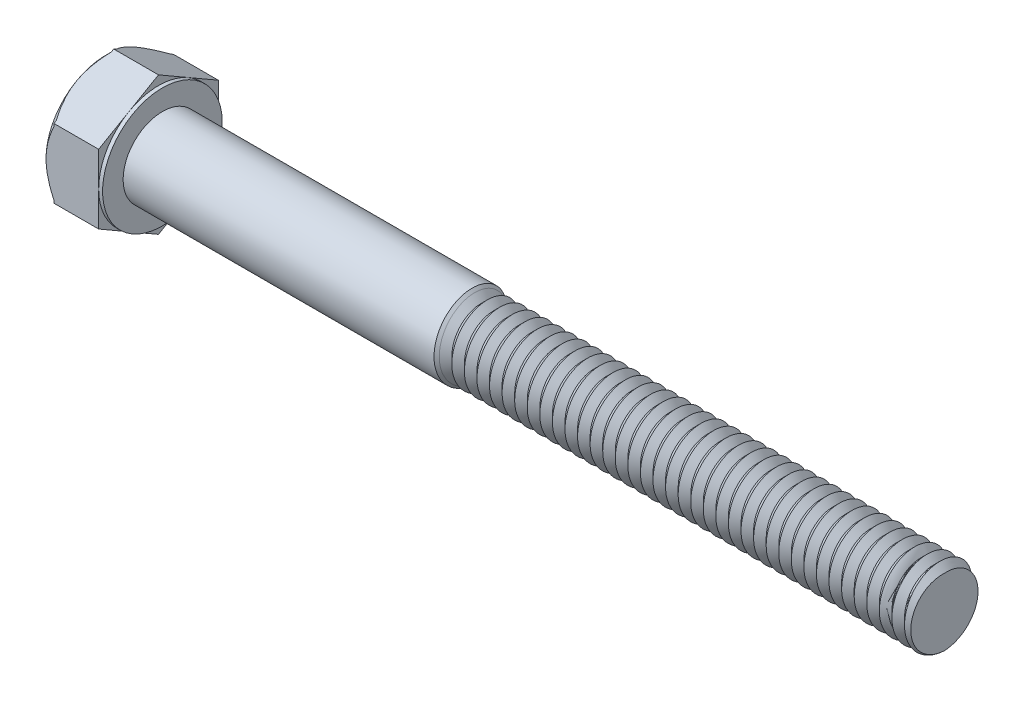
SolidWorks part; units mm, degrees
material "Plain Carbon Steel"
ref_plane "Front Plane" through (0, 0, 0) normal (0, 0, 1) x (1, 0, 0)
ref_plane "Top Plane" through (0, 0, 0) normal (0, 1, 0) x (1, 0, 0)
ref_plane "Right Plane" through (0, 0, 0) normal (1, 0, 0) x (0, 0, -1)
sketch "Sketch3" plane through (0, 0, 0) normal (1, 0, 0) x (0, 0, -1)
  line L1 (0, -4.395) -> (3.8062, -2.1975)
  line L2 (3.8062, -2.1975) -> (3.8062, 2.1975)
  line L3 (3.8062, 2.1975) -> (0, 4.395)
  line L4 (0, 4.395) -> (-3.8062, 2.1975)
  line L5 (-3.8062, 2.1975) -> (-3.8062, -2.1975)
  line L6 (-3.8062, -2.1975) -> (0, -4.395)
  circle A0 centre (0, 0) radius 3.8062 construction
  dimension "D1" = 8.79
extrude "Boss-Extrude1" add sketch "Sketch3" along normal mid plane 3.35
sketch "Sketch4" plane through (1.675, 0, 0) normal (1, 0, 0) x (0, 0, -1)
  circle A0 centre (0, 0) radius 2.5
  dimension "D1" = 5
extrude "Boss-Extrude2" add sketch "Sketch4" along normal blind 50
sketch "Sketch5" plane through (0, 0, 0) normal (0, 0, 1) x (1, 0, 0)
  line L0 (52.2407, 2.5) -> (51.675, 1.9343)
  line L1 (51.675, 1.9343) -> (51.1093, 2.5)
  line L2 (51.675, 2.5) -> (1.675, 2.5) construction
  line L3 (51.1093, 2.5) -> (51.675, 3.0657)
  line L4 (51.675, 3.0657) -> (52.2407, 2.5)
  line L5 (51.675, -2.5) -> (51.675, 2.5) construction
  dimension "D1" = 45
  dimension "D2" = 0.8
sketch "Sketch6" plane through (51.675, 0, 0) normal (1, 0, 0) x (0, 0, -1)
  circle A0 centre (0, 0) radius 2.5
curve "Helix/Spiral1" pitch 0.8 height 30 radius 2.5 centre (51.675, 0, 0) axis (-1, 0, 0) start towards (0, 0.7071, 0.7071)
sweep "Cut-Sweep1" cut profiles "Sketch5" path "Helix/Spiral1" align with end faces yes
sketch "Sketch7" plane through (-1.675, 0, 0) normal (-1, 0, 0) x (0, 0, 1)
  circle A0 centre (0, 0) radius 3.8062
extrude "Cut-Extrude3" cut sketch "Sketch7" against normal blind 0.5 draft 45 flip side to cut
sketch "Sketch8" plane through (1.675, 0, 0) normal (1, 0, 0) x (0, 0, -1)
  circle A0 centre (0, 0) radius 3.8062
extrude "Boss-Extrude3" add sketch "Sketch8" along normal blind 0.25
